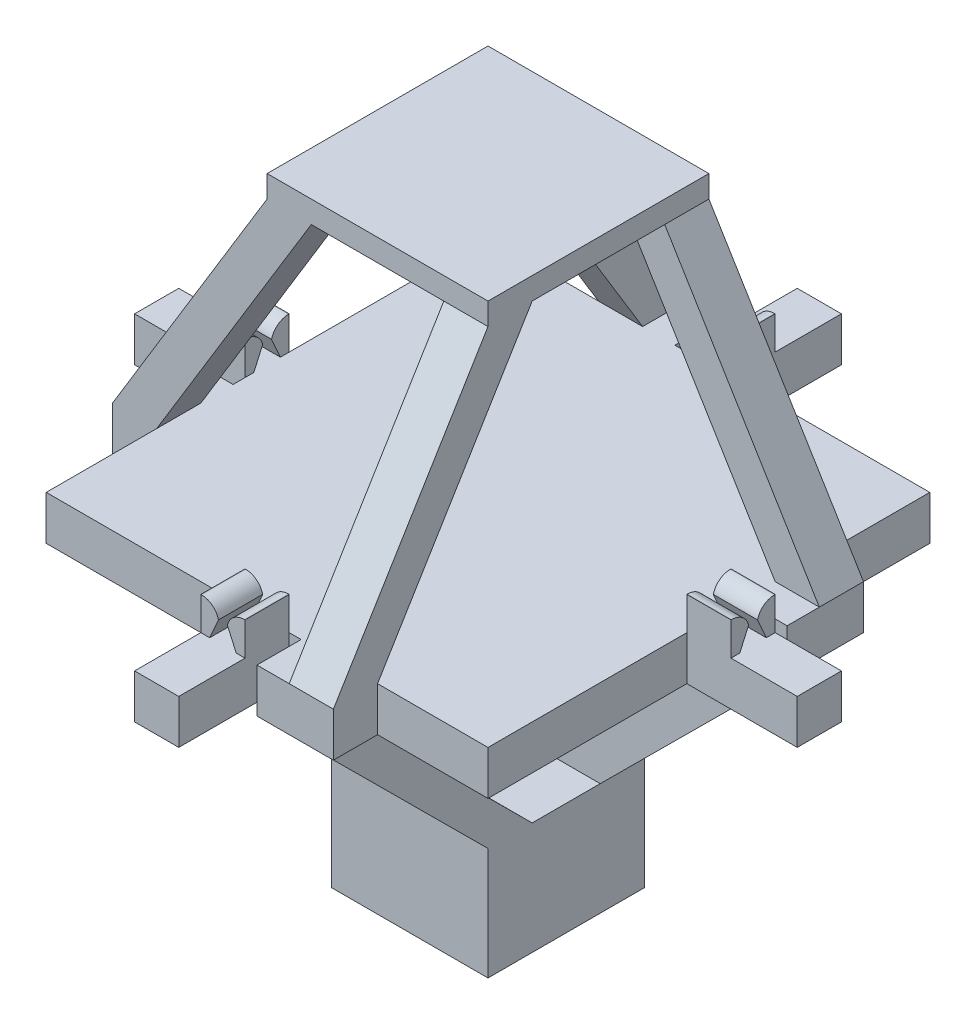
SolidWorks part; units mm, degrees
ref_plane "Front Plane" through (0, 0, 0) normal (0, 0, 1) x (1, 0, 0)
ref_plane "Top Plane" through (0, 0, 0) normal (0, 1, 0) x (1, 0, 0)
ref_plane "Right Plane" through (0, 0, 0) normal (1, 0, 0) x (0, 0, -1)
sketch "Sketch2" plane through (0, 0, 0) normal (0, 1, 0) x (1, 0, 0)
  line L1 (-50, -50) -> (50, -50)
  line L2 (-50, -50) -> (-50, 50)
  line L3 (-50, 50) -> (50, 50)
  line L4 (50, -50) -> (50, 50)
  line L5 (-50, -50) -> (50, 50) construction
  line L6 (-50, 50) -> (50, -50) construction
  point P0 (0, 0)
extrude "Boss-Extrude1" add sketch "Sketch2" along normal blind 5
sketch "Sketch3" plane through (0, 0, 0) normal (0, -1, 0) x (1, 0, 0)
  line L1 (-50, -50) -> (50, -50)
  line L2 (-50, -50) -> (-50, 50)
  line L3 (-50, 50) -> (50, 50)
  line L4 (50, -50) -> (50, 50)
  line L5 (-50, -50) -> (50, 50) construction
  line L6 (-50, 50) -> (50, -50) construction
  point P0 (0, 0)
extrude "Boss-Extrude2" add sketch "Sketch3" along normal blind 5
sketch "Sketch8" plane through (0, -5, 0) normal (0, -1, 0) x (1, 0, 0)
  circle A0 centre (0, 0) radius 5
extrude "Boss-Extrude7" add sketch "Sketch8" along normal blind 30
sketch "Sketch11" plane through (50, 0, 0) normal (1, 0, 0) x (0, 0, -1)
  line L0 (5, -5) -> (5, 12.5)
  line L3 (-5, -5) -> (5, -5)
  line L5 (5, 12.5) -> (1, 12.5)
  line L6 (1, 12.5) -> (1, 9.5)
  line L7 (-5, -5) -> (-5, 12.5)
  line L8 (-5, 12.5) -> (-1, 12.5)
  line L9 (-1, 12.5) -> (-1, 9.5)
  line L10 (-50, 5) -> (50, 5) construction
  line L11 (-1, 9.5) -> (-3, 5)
  line L12 (-3, 5) -> (3, 5)
  line L13 (3, 5) -> (1, 9.5)
  point P0 (0, 0)
  point P8 (3, 5)
  point P12 (-3, 5)
extrude "Boss-Extrude21" add sketch "Sketch11" along normal blind 10
fillet "Fillet14" radius 4 1 edges at (55, 12.5, -1)
fillet "Fillet13" radius 4 1 edges at (55, 12.5, 1)
sketch "Sketch24" plane through (60, 0, 0) normal (1, 0, 0) x (0, 0, -1)
  line L1 (-5, 5) -> (5, 5)
  line L2 (-5, 5) -> (-5, -5)
  line L3 (-5, -5) -> (5, -5)
  line L4 (5, 5) -> (5, -5)
  line L5 (-5, 5) -> (5, -5) construction
  line L6 (-5, -5) -> (5, 5) construction
  point P0 (0, 0)
extrude "Boss-Extrude22" add sketch "Sketch24" along normal blind 15
sketch "Sketch13" plane through (-50, 0, 0) normal (-1, 0, 0) x (0, 0, 1)
  line L0 (50, -5) -> (-50, -5) construction
  line L2 (-5, 12.5) -> (-5, -5)
  line L3 (-5, -5) -> (5, -5)
  line L4 (5, 12.5) -> (5, -5)
  line L5 (5, 12.5) -> (1, 12.5)
  line L6 (1, 12.5) -> (1, 9.5)
  line L7 (-5, 12.5) -> (-1, 12.5)
  line L8 (-1, 12.5) -> (-1, 9.5)
  line L9 (-1, 9.5) -> (-3, 5)
  line L10 (-3, 5) -> (3, 5)
  line L11 (3, 5) -> (1, 9.5)
  point P0 (0, 0)
  point P8 (-3, 5)
  point P13 (3, 5)
extrude "Boss-Extrude25" add sketch "Sketch13" along normal blind 10
sketch "Sketch26" plane through (-60, 0, 0) normal (-1, 0, 0) x (0, 0, 1)
  line L0 (-5, -5) -> (5, -5) construction
  line L1 (-5, 5) -> (5, 5)
  line L2 (-5, 5) -> (-5, -5)
  line L3 (-5, -5) -> (5, -5)
  line L4 (5, 5) -> (5, -5)
  line L5 (-5, 5) -> (5, -5) construction
  line L6 (-5, -5) -> (5, 5) construction
  line L7 (-5, -5) -> (5, -5) construction
  point P0 (0, 0)
extrude "Boss-Extrude26" add sketch "Sketch26" along normal blind 15
fillet "Fillet18" radius 4 1 edges at (-55, 12.5, 1)
fillet "Fillet17" radius 4 1 edges at (-55, 12.5, -1)
sketch "Sketch14" plane through (0, 0, -50) normal (0, 0, -1) x (-1, 0, 0)
  line L0 (-5, 12.5) -> (-1, 12.5)
  line L2 (-5, 12.5) -> (-5, -5)
  line L3 (-5, -5) -> (5, -5)
  line L4 (5, 12.5) -> (5, -5)
  line L5 (5, 12.5) -> (1, 12.5)
  line L6 (-1, 12.5) -> (-1, 9.5)
  line L7 (1, 12.5) -> (1, 9.5)
  line L8 (-50, 5) -> (50, 5) construction
  line L9 (-1, 9.5) -> (-3, 5)
  line L10 (-3, 5) -> (3, 5)
  line L11 (3, 5) -> (1, 9.5)
  point P0 (0, 0)
  point P11 (3, 5)
  point P12 (-3, 5)
extrude "Boss-Extrude23" add sketch "Sketch14" along normal blind 10
sketch "Sketch25" plane through (0, 0, -60) normal (0, 0, -1) x (-1, 0, 0)
  line L1 (-5, 5) -> (5, 5)
  line L2 (-5, 5) -> (-5, -5)
  line L3 (-5, -5) -> (5, -5)
  line L4 (5, 5) -> (5, -5)
  line L5 (-5, 5) -> (5, -5) construction
  line L6 (-5, -5) -> (5, 5) construction
  point P0 (0, 0)
extrude "Boss-Extrude24" add sketch "Sketch25" along normal blind 15
fillet "Fillet15" radius 4 1 edges at (-1, 12.5, -55)
fillet "Fillet16" radius 4 1 edges at (1, 12.5, -55)
sketch "Sketch12" plane through (0, 0, 50) normal (0, 0, 1) x (1, 0, 0)
  line L0 (50, -5) -> (-50, -5) construction
  line L2 (-5, 12.5) -> (-5, -5)
  line L3 (-5, -5) -> (5, -5)
  line L4 (5, 12.5) -> (5, -5)
  line L5 (5, 12.5) -> (1, 12.5)
  line L6 (1, 12.5) -> (1, 9.5)
  line L7 (-5, -5) -> (5, -5) construction
  line L8 (-5, 12.5) -> (-1, 12.5)
  line L9 (-1, 12.5) -> (-1, 9.5)
  line L10 (-1, 9.5) -> (-3, 5)
  line L11 (-3, 5) -> (3, 5)
  line L12 (3, 5) -> (1, 9.5)
  point P0 (0, 0)
  point P10 (-3, 5)
  point P15 (3, 5)
extrude "Boss-Extrude10" add sketch "Sketch12" along normal blind 10
fillet "Fillet19" radius 4 1 edges at (-1, 12.5, 55)
sketch "Sketch27" plane through (0, 0, 60) normal (0, 0, 1) x (1, 0, 0)
  line L1 (-5, 5) -> (5, 5)
  line L2 (-5, 5) -> (-5, -5)
  line L3 (-5, -5) -> (5, -5)
  line L4 (5, 5) -> (5, -5)
  line L5 (-5, 5) -> (5, -5) construction
  line L6 (-5, -5) -> (5, 5) construction
  point P0 (0, 0)
extrude "Boss-Extrude27" add sketch "Sketch27" along normal blind 15
fillet "Fillet20" radius 4 1 edges at (1, 12.5, 55)
ref_plane "Plane4" through (0, 72.5, 0) normal (0, 1, 0) x (1, 0, 0)
ref_plane "Plane5" through (0, -72.5, 0) normal (0, 1, 0) x (1, 0, 0)
sketch "Sketch62" plane through (0, -5, 0) normal (0, -1, 0) x (1, 0, 0)
  circle A0 centre (0, 0) radius 11.2235
extrude "Cut-Extrude3" cut sketch "Sketch62" along normal blind 30
sketch "Sketch64" plane through (0, -72.5, 0) normal (0, 1, 0) x (1, 0, 0)
  line L2 (17.7, 17.7) -> (-17.7, 17.7)
  line L3 (17.7, 17.7) -> (17.7, -17.7)
  line L4 (17.7, -17.7) -> (-17.7, -17.7)
  line L5 (-17.7, 17.7) -> (-17.7, -17.7)
  line L6 (17.7, 17.7) -> (-17.7, -17.7) construction
  line L7 (17.7, -17.7) -> (-17.7, 17.7) construction
  point P1 (0, 0)
extrude "Boss-Extrude53" add sketch "Sketch64" along normal blind 25.4 separate body
sketch "Sketch66" plane through (0, -72.5, 0) normal (0, -1, 0) x (-1, 0, 0)
  line L1 (12.7, -12.7) -> (-12.7, -12.7)
  line L2 (12.7, -12.7) -> (12.7, 12.7)
  line L3 (12.7, 12.7) -> (-12.7, 12.7)
  line L4 (-12.7, -12.7) -> (-12.7, 12.7)
  line L5 (12.7, -12.7) -> (-12.7, 12.7) construction
  line L6 (12.7, 12.7) -> (-12.7, -12.7) construction
  point P0 (0, 0)
extrude "Cut-Extrude4" cut sketch "Sketch66" against normal blind 12.7
ref_plane "Plane6" through (0, 67.5, 0) normal (0, 1, 0) x (1, 0, 0)
sketch "Sketch67" plane through (0, 67.5, 0) normal (0, 1, 0) x (1, 0, 0)
  line L1 (-25, 25) -> (25, 25)
  line L2 (-25, 25) -> (-25, -25)
  line L3 (-25, -25) -> (25, -25)
  line L4 (25, 25) -> (25, -25)
  line L5 (-25, 25) -> (25, -25) construction
  line L6 (-25, -25) -> (25, 25) construction
  point P0 (0, 0)
extrude "Boss-Extrude54" add sketch "Sketch67" against normal blind 5 separate body
sketch "Sketch68" plane through (0, 0, 50) normal (0, 0, 1) x (1, 0, 0)
  line L0 (5, 5) -> (50, 5) construction
  line L1 (50, -5) -> (5, -5) construction
  line L2 (7.7, -5) -> (25, -5)
  line L3 (25, -5) -> (25, 5)
  line L4 (25, 5) -> (7.7, 5)
  line L5 (7.7, 5) -> (7.7, -5)
  point P0 (25, 5)
  point P1 (15, 5)
  point P4 (15, 5)
  point P5 (17.7, -5)
  point P6 (7.7, -5)
extrude "Boss-Extrude55" add sketch "Sketch68" along normal blind 10
sketch "Sketch70" plane through (0, 0, -50) normal (0, 0, -1) x (-1, 0, 0)
  line L0 (5, 5) -> (50, 5) construction
  line L1 (25, 5) -> (7.7, 5)
  line L2 (7.7, 5) -> (7.7, -5)
  line L3 (50, -5) -> (5, -5) construction
  line L4 (7.7, -5) -> (25, -5)
  line L5 (25, -5) -> (25, 5)
  point P0 (25, 5)
extrude "Boss-Extrude57" add sketch "Sketch70" along normal blind 10
sketch "Sketch74" plane through (-50, 0, 0) normal (-1, 0, 0) x (0, 0, 1)
  line L0 (5, 5) -> (50, 5) construction
  line L1 (25, 5) -> (7.7, 5)
  line L2 (7.7, 5) -> (7.7, -5)
  line L3 (50, -5) -> (5, -5) construction
  line L4 (7.7, -5) -> (25, -5)
  line L5 (25, -5) -> (25, 5)
  point P0 (25, 5)
extrude "Boss-Extrude58" add sketch "Sketch74" along normal blind 10
sketch "Sketch76" plane through (-17.7, 0, 0) normal (-1, 0, 0) x (0, 0, 1)
  line L0 (-17.7, -47.1) -> (-60, -5)
  line L1 (-60, -5) -> (-50, -5)
  line L2 (-60, -5) -> (-50, -5) construction
  line L3 (-50, -5) -> (-7.7, -47.1)
  line L4 (-17.7, -47.1) -> (17.7, -47.1) construction
  line L5 (-7.7, -47.1) -> (-17.7, -47.1)
extrude "Boss-Extrude59" add sketch "Sketch76" against normal blind 10
sketch "Sketch77" plane through (-25, 0, 0) normal (-1, 0, 0) x (0, 0, 1)
  line L0 (-25, 62.5) -> (-60, 5)
  line L1 (-60, 5) -> (-50, 5)
  line L2 (-25, 62.5) -> (-15, 62.5)
  line L3 (-25, 62.5) -> (25, 62.5) construction
  line L4 (-15, 62.5) -> (-50, 5)
extrude "Boss-Extrude60" add sketch "Sketch77" against normal blind 10
sketch "Sketch78" plane through (0, 0, 17.7) normal (0, 0, 1) x (1, 0, 0)
  line L0 (-17.7, -47.1) -> (-60, -5)
  line L1 (-60, -5) -> (-50, -5)
  line L2 (-50, -5) -> (-7.7, -47.1)
  line L3 (-7.7, -47.1) -> (-17.7, -47.1)
extrude "Boss-Extrude61" add sketch "Sketch78" against normal blind 10
sketch "Sketch79" plane through (0, 0, 25) normal (0, 0, 1) x (1, 0, 0)
  line L0 (-25, 62.5) -> (-60, 5)
  line L1 (-60, 5) -> (-50, 5)
  line L2 (-50, 5) -> (-15, 62.5)
  line L3 (-15, 62.5) -> (-25, 62.5)
extrude "Boss-Extrude62" add sketch "Sketch79" against normal blind 10
sketch "Sketch82" plane through (17.7, 0, 0) normal (1, 0, 0) x (0, 0, -1)
  line L0 (-60, -5) -> (-17.7, -47.1)
  line L1 (-17.7, -47.1) -> (-7.7, -47.1)
  line L2 (-7.7, -47.1) -> (-50, -5)
  line L3 (-50, -5) -> (-60, -5)
extrude "Boss-Extrude63" add sketch "Sketch82" against normal blind 10
sketch "Sketch83" plane through (25, 0, 0) normal (1, 0, 0) x (0, 0, -1)
  line L0 (-25, 62.5) -> (-60, 5)
  line L1 (-60, 5) -> (-50, 5)
  line L2 (-50, 5) -> (-15, 62.5)
  line L3 (-15, 62.5) -> (-25, 62.5)
extrude "Boss-Extrude64" add sketch "Sketch83" against normal blind 10
sketch "Sketch85" plane through (50, 0, 0) normal (1, 0, 0) x (0, 0, -1)
  line L0 (5, 5) -> (50, 5) construction
  line L1 (25, 5) -> (7.7, 5)
  line L2 (7.7, 5) -> (7.7, -5)
  line L4 (50, -5) -> (5, -5) construction
  line L5 (7.7, -5) -> (25, -5)
  line L6 (25, -5) -> (25, 5)
  point P0 (25, 5)
extrude "Boss-Extrude65" add sketch "Sketch85" along normal blind 10
sketch "Sketch86" plane through (0, 0, -25) normal (0, 0, -1) x (-1, 0, 0)
  line L0 (-25, 62.5) -> (-60, 5)
  line L1 (-60, 5) -> (-50, 5)
  line L2 (-50, 5) -> (-15, 62.5)
  line L3 (-15, 62.5) -> (-25, 62.5)
extrude "Boss-Extrude66" add sketch "Sketch86" against normal blind 10
sketch "Sketch89" plane through (0, 0, -17.7) normal (0, 0, -1) x (-1, 0, 0)
  line L0 (-60, -5) -> (-50, -5)
  line L1 (-50, -5) -> (-7.7, -47.1)
  line L2 (-7.7, -47.1) -> (-17.7, -47.1)
  line L3 (-17.7, -47.1) -> (-60, -5)
extrude "Boss-Extrude67" add sketch "Sketch89" against normal blind 10
